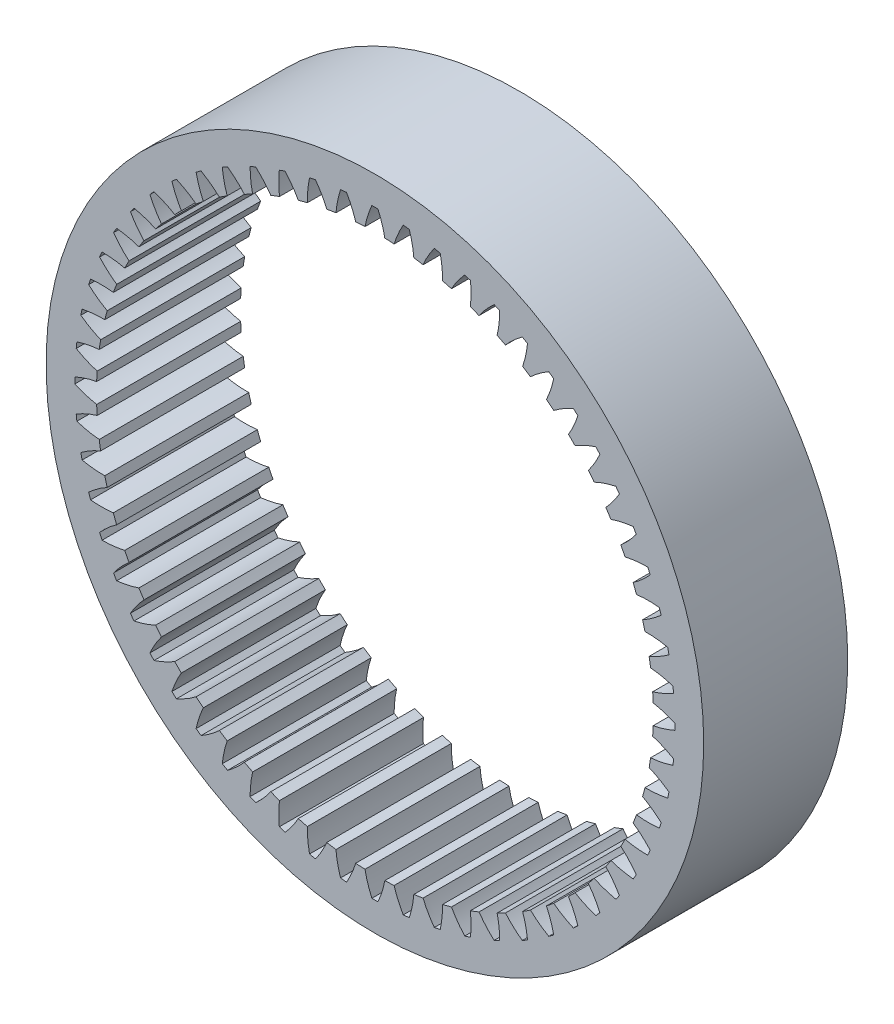
SolidWorks part; units mm, degrees
ref_plane "中间平面" through (0, 0, 0) normal (0, 0, 1) x (1, 0, 0)
ref_plane "上视基准面" through (0, 0, 0) normal (0, 1, 0) x (1, 0, 0)
ref_plane "右视基准面" through (0, 0, 0) normal (1, 0, 0) x (0, 0, -1)
sketch "直内齿圈" plane through (0, 0, 0) normal (0, 0, 1) x (1, 0, 0)
  line L2 (2.2167, 56.338) -> (0, 0)
  line L3 (0, 0) -> (0, 52) construction
  line L6 (0, 0) -> (-2.2167, 56.338)
  circle A0 centre (0, 0) radius 56.3816
  circle A1 centre (0, 0) radius 58
  arc A2 (1.5706, 59.9794) -> (-1.5706, 59.9794) centre (0, 0) ccw
  circle A3 centre (0, 0) radius 62.5
  spline S0 degree 4 poles (2.2167, 56.338) (2.2189, 56.3915) (2.2208, 56.4987) (2.2154, 56.7131) (2.1931, 57.034) (2.1521, 57.4071) (2.076, 57.9166) (1.9626, 58.5073) (1.7599, 59.3651) (1.3841, 60.63) (0.7981, 62.1958) (0.0262, 63.8633) (-0.8365, 65.4532) (-1.8681, 67.1454) (-3.5464, 69.5933) (-6.5827, 73.2746) (-11.389, 77.7718) (-17.974, 82.3547) (-25.6821, 86.2657) (-33.81, 89.1926) (-42.2136, 91.1824) (-51.2003, 92.337) (-62.4178, 92.599) (-75.7449, 91.194) (-90.8317, 87.3175) (-104.7363, 81.3291) (-115.9321, 74.8155) (-126.4728, 67.3125) (-134.6739, 60.2977) (-142.2457, 52.6107) (-149.1555, 44.336) (-154.2755, 37.3963) (-160.155, 28.3611) (-164.812, 19.8424) (-168.4497, 12.0205) (-171.2543, 5.0188) (-172.7487, 0.9762) (-174.1349, -3.1048) (-175.4127, -7.221) (-176.5824, -11.3691) (-177.6441, -15.5464) (-178.598, -19.7492) (-179.3387, -23.4474) (-179.9066, -26.6288) (-180.3354, -29.289) (-180.6516, -31.4183) (-180.9054, -33.2908) (-181.1057, -34.8874) (-181.2627, -36.2365) (-181.3797, -37.2858) (-181.5021, -38.4742) (-181.617, -39.6294) (-181.7424, -41.0512) (-181.8433, -42.2423) (-181.9548, -43.771) (-182.014, -44.6462) (-182.0826, -45.7524) (-182.1302, -46.5966) (-182.1867, -47.6884) (-182.2454, -48.9883) (-182.3019, -50.5105) (-182.3493, -52.2479) (-182.38, -53.9871) (-182.3939, -55.7257) (-182.3911, -57.4649) (-182.3716, -59.2037) (-182.3354, -60.9423) (-182.2827, -62.6805) (-182.2134, -64.4181) (-182.1277, -66.1549) (-182.0255, -67.8909) (-181.907, -69.6258) (-181.8059, -70.9261) (-181.733, -71.7926) (-181.6953, -72.2256) knots 0 0 0 0 0 0.000701 0.001401 0.002802 0.004203 0.005604 0.008133 0.010661 0.015718 0.022839 0.02996 0.034653 0.039347 0.048734 0.068727 0.096889 0.125051 0.153212 0.181374 0.209535 0.237696 0.271429 0.327752 0.384075 0.440398 0.46856 0.496721 0.553044 0.581206 0.609367 0.637529 0.66569 0.722013 0.736094 0.750174 0.764255 0.778336 0.792417 0.806497 0.820578 0.834659 0.84874 0.85578 0.86282 0.869861 0.876901 0.880421 0.883942 0.887462 0.890982 0.895509 0.900036 0.904564 0.909091 0.911932 0.914773 0.917614 0.920455 0.926136 0.931818 0.9375 0.943182 0.948864 0.954545 0.960227 0.965909 0.971591 0.977273 0.982955 0.988636 0.994318 1 1 1 1 1 construction
  spline S1 degree 4 poles (2.2167, 56.338) (2.2189, 56.3915) (2.2208, 56.4987) (2.2154, 56.7131) (2.1931, 57.034) (2.1521, 57.4071) (2.076, 57.9166) (1.9626, 58.5073) (1.7599, 59.3651) (1.3841, 60.63) (0.7981, 62.1958) (0.0262, 63.8633) (-0.8365, 65.4532) (-1.8681, 67.1454) (-3.5464, 69.5933) (-6.5827, 73.2746) (-11.389, 77.7718) (-17.974, 82.3547) (-25.6821, 86.2657) (-33.81, 89.1926) (-42.2136, 91.1824) (-51.2003, 92.337) (-62.4178, 92.599) (-75.7449, 91.194) (-90.8317, 87.3175) (-104.7363, 81.3291) (-115.9321, 74.8155) (-126.4728, 67.3125) (-134.6739, 60.2977) (-142.2457, 52.6107) (-149.1555, 44.336) (-154.2755, 37.3963) (-160.155, 28.3611) (-164.812, 19.8424) (-168.4497, 12.0205) (-171.2543, 5.0188) (-172.7487, 0.9762) (-174.1349, -3.1048) (-175.4127, -7.221) (-176.5824, -11.3691) (-177.6441, -15.5464) (-178.598, -19.7492) (-179.3387, -23.4474) (-179.9066, -26.6288) (-180.3354, -29.289) (-180.6516, -31.4183) (-180.9054, -33.2908) (-181.1057, -34.8874) (-181.2627, -36.2365) (-181.3797, -37.2858) (-181.5021, -38.4742) (-181.617, -39.6294) (-181.7424, -41.0512) (-181.8433, -42.2423) (-181.9355, -43.5066) (-181.9779, -44.1172) (-181.9987, -44.4314) knots 0 0 0 0 0 0.000701 0.001401 0.002802 0.004203 0.005604 0.008133 0.010661 0.015718 0.022839 0.02996 0.034653 0.039347 0.048734 0.068727 0.096889 0.125051 0.153212 0.181374 0.209535 0.237696 0.271429 0.327752 0.384075 0.440398 0.46856 0.496721 0.553044 0.581206 0.609367 0.637529 0.66569 0.722013 0.736094 0.750174 0.764255 0.778336 0.792417 0.806497 0.820578 0.834659 0.84874 0.85578 0.86282 0.869861 0.876901 0.880421 0.883942 0.887462 0.890982 0.895509 0.900036 0.904564 0.909091 0.909091 0.909091 0.909091 0.909091
  spline S2 degree 4 poles (-2.2167, 56.338) (-2.2189, 56.3915) (-2.2208, 56.4987) (-2.2154, 56.7131) (-2.1931, 57.034) (-2.1521, 57.4071) (-2.076, 57.9166) (-1.9626, 58.5073) (-1.7599, 59.3651) (-1.3841, 60.63) (-0.7981, 62.1958) (-0.0262, 63.8633) (0.8365, 65.4532) (1.8681, 67.1454) (3.5464, 69.5933) (6.5827, 73.2746) (11.389, 77.7718) (17.974, 82.3547) (25.6821, 86.2657) (33.81, 89.1926) (42.2136, 91.1824) (51.2003, 92.337) (62.4178, 92.599) (75.7449, 91.194) (90.8317, 87.3175) (104.7363, 81.3291) (115.9321, 74.8155) (126.4728, 67.3125) (134.6739, 60.2977) (142.2457, 52.6107) (149.1555, 44.336) (154.2755, 37.3963) (160.155, 28.3611) (164.812, 19.8424) (168.4497, 12.0205) (171.2543, 5.0188) (172.7487, 0.9762) (174.1349, -3.1048) (175.4127, -7.221) (176.5824, -11.3691) (177.6441, -15.5464) (178.598, -19.7492) (179.3387, -23.4474) (179.9066, -26.6288) (180.3354, -29.289) (180.6516, -31.4183) (180.9054, -33.2908) (181.1057, -34.8874) (181.2627, -36.2365) (181.3797, -37.2858) (181.5021, -38.4742) (181.617, -39.6294) (181.7424, -41.0512) (181.8433, -42.2423) (181.9548, -43.771) (182.014, -44.6462) (182.0826, -45.7524) (182.1302, -46.5966) (182.1867, -47.6884) (182.2454, -48.9883) (182.3019, -50.5105) (182.3493, -52.2479) (182.38, -53.9871) (182.3939, -55.7257) (182.3911, -57.4649) (182.3716, -59.2037) (182.3354, -60.9423) (182.2827, -62.6805) (182.2134, -64.4181) (182.1277, -66.1549) (182.0255, -67.8909) (181.907, -69.6258) (181.8059, -70.9261) (181.733, -71.7926) (181.6953, -72.2256) knots 0 0 0 0 0 0.000701 0.001401 0.002802 0.004203 0.005604 0.008133 0.010661 0.015718 0.022839 0.02996 0.034653 0.039347 0.048734 0.068727 0.096889 0.125051 0.153212 0.181374 0.209535 0.237696 0.271429 0.327752 0.384075 0.440398 0.46856 0.496721 0.553044 0.581206 0.609367 0.637529 0.66569 0.722013 0.736094 0.750174 0.764255 0.778336 0.792417 0.806497 0.820578 0.834659 0.84874 0.85578 0.86282 0.869861 0.876901 0.880421 0.883942 0.887462 0.890982 0.895509 0.900036 0.904564 0.909091 0.911932 0.914773 0.917614 0.920455 0.926136 0.931818 0.9375 0.943182 0.948864 0.954545 0.960227 0.965909 0.971591 0.977273 0.982955 0.988636 0.994318 1 1 1 1 1 construction
  spline S3 degree 4 poles (-2.2167, 56.338) (-2.2189, 56.3915) (-2.2208, 56.4987) (-2.2154, 56.7131) (-2.1931, 57.034) (-2.1521, 57.4071) (-2.076, 57.9166) (-1.9626, 58.5073) (-1.7599, 59.3651) (-1.3841, 60.63) (-0.7981, 62.1958) (-0.0262, 63.8633) (0.8365, 65.4532) (1.8681, 67.1454) (3.5464, 69.5933) (6.5827, 73.2746) (11.389, 77.7718) (17.974, 82.3547) (25.6821, 86.2657) (33.81, 89.1926) (42.2136, 91.1824) (51.2003, 92.337) (62.4178, 92.599) (75.7449, 91.194) (90.8317, 87.3175) (104.7363, 81.3291) (115.9321, 74.8155) (126.4728, 67.3125) (134.6739, 60.2977) (142.2457, 52.6107) (149.1555, 44.336) (154.2755, 37.3963) (160.155, 28.3611) (164.812, 19.8424) (168.4497, 12.0205) (171.2543, 5.0188) (172.7487, 0.9762) (174.1349, -3.1048) (175.4127, -7.221) (176.5824, -11.3691) (177.6441, -15.5464) (178.598, -19.7492) (179.3387, -23.4474) (179.9066, -26.6288) (180.3354, -29.289) (180.6516, -31.4183) (180.9054, -33.2908) (181.1057, -34.8874) (181.2627, -36.2365) (181.3797, -37.2858) (181.5021, -38.4742) (181.617, -39.6294) (181.7424, -41.0512) (181.8433, -42.2423) (181.9355, -43.5066) (181.9779, -44.1172) (181.9987, -44.4314) knots 0 0 0 0 0 0.000701 0.001401 0.002802 0.004203 0.005604 0.008133 0.010661 0.015718 0.022839 0.02996 0.034653 0.039347 0.048734 0.068727 0.096889 0.125051 0.153212 0.181374 0.209535 0.237696 0.271429 0.327752 0.384075 0.440398 0.46856 0.496721 0.553044 0.581206 0.609367 0.637529 0.66569 0.722013 0.736094 0.750174 0.764255 0.778336 0.792417 0.806497 0.820578 0.834659 0.84874 0.85578 0.86282 0.869861 0.876901 0.880421 0.883942 0.887462 0.890982 0.895509 0.900036 0.904564 0.909091 0.909091 0.909091 0.909091 0.909091
  point P8 (0, 60)
  dimension "基圆直径" = 112.7631
  dimension "齿顶圆" = 116
  dimension "分度圆" = 120
  dimension "齿根圆" = 125
  dimension "D1" = 3.1416
sketch "圆" plane through (0, 0, 0) normal (0, 0, 1) x (1, 0, 0)
  circle A1 centre (0, 0) radius 68.5
  circle A2 centre (0, 0) radius 58 construction
  circle A3 centre (0, 0) radius 58
  dimension "D1" = 137
extrude "毛胚" add sketch "圆" along normal mid plane 30
chamfer "轮齿倒角" [suppressed] distance 0.001 angle 45
sketch "齿形" plane through (0, 0, 0) normal (0, 0, 1) x (1, 0, 0)
  line L4 (0, 0) -> (-2.2167, 56.338) construction
  line L5 (2.2167, 56.338) -> (0, 0) construction
  line L6 (0, 0) -> (-2.2167, 56.338)
  line L7 (2.2167, 56.338) -> (0, 0)
  circle A4 centre (0, 0) radius 58 construction
  circle A5 centre (0, 0) radius 62.5 construction
  circle A6 centre (0, 0) radius 58
  circle A7 centre (0, 0) radius 62.5
  spline S1 degree 4 poles (-1995.8108, -87.8377) (43.9441, 50.7725) (-0.8416, 50.9897) (-2.4035, 54.0015) (-2.1931, 57.034) (-2.1521, 57.4071) (-2.076, 57.9166) (-1.9626, 58.5073) (-1.7599, 59.3651) (-1.3841, 60.63) (-0.7981, 62.1958) (-0.0262, 63.8633) (0.8365, 65.4532) (1.8681, 67.1454) (3.5464, 69.5933) (6.5827, 73.2746) (11.389, 77.7718) (17.974, 82.3547) (25.6821, 86.2657) (33.81, 89.1926) (42.2136, 91.1824) (51.2003, 92.337) (62.4178, 92.599) (75.7449, 91.194) (90.8317, 87.3175) (104.7363, 81.3291) (115.9321, 74.8155) (126.4728, 67.3125) (134.6739, 60.2977) (142.2457, 52.6107) (149.1555, 44.336) (154.2755, 37.3963) (160.155, 28.3611) (164.812, 19.8424) (168.4497, 12.0205) (171.2543, 5.0188) (172.7487, 0.9762) (174.1349, -3.1048) (175.4127, -7.221) (176.5824, -11.3691) (177.6441, -15.5464) (178.598, -19.7492) (179.3387, -23.4474) (179.9066, -26.6288) (180.3354, -29.289) (180.6516, -31.4183) (180.9054, -33.2908) (181.1057, -34.8874) (181.2627, -36.2365) (181.3797, -37.2858) (181.5021, -38.4742) (181.617, -39.6294) (181.7424, -41.0512) (182.1176, -45.4798) (182.8201, -57.5451) (176.7388, 30.3447) (313.9302, -2039.1996) knots -0.035513 -0.035513 -0.035513 -0.035513 -0.035513 0.000701 0.001401 0.002802 0.004203 0.005604 0.008133 0.010661 0.015718 0.022839 0.02996 0.034653 0.039347 0.048734 0.068727 0.096889 0.125051 0.153212 0.181374 0.209535 0.237696 0.271429 0.327752 0.384075 0.440398 0.46856 0.496721 0.553044 0.581206 0.609367 0.637529 0.66569 0.722013 0.736094 0.750174 0.764255 0.778336 0.792417 0.806497 0.820578 0.834659 0.84874 0.85578 0.86282 0.869861 0.876901 0.880421 0.883942 0.887462 0.890982 0.895509 0.900036 0.904564 0.958315 0.958315 0.958315 0.958315 0.958315 only from (-2.2167, 56.338) to (181.9987, -44.4314) construction
  spline S3 degree 4 poles (1995.8108, -87.8377) (-43.9441, 50.7725) (0.8416, 50.9897) (2.4035, 54.0015) (2.1931, 57.034) (2.1521, 57.4071) (2.076, 57.9166) (1.9626, 58.5073) (1.7599, 59.3651) (1.3841, 60.63) (0.7981, 62.1958) (0.0262, 63.8633) (-0.8365, 65.4532) (-1.8681, 67.1454) (-3.5464, 69.5933) (-6.5827, 73.2746) (-11.389, 77.7718) (-17.974, 82.3547) (-25.6821, 86.2657) (-33.81, 89.1926) (-42.2136, 91.1824) (-51.2003, 92.337) (-62.4178, 92.599) (-75.7449, 91.194) (-90.8317, 87.3175) (-104.7363, 81.3291) (-115.9321, 74.8155) (-126.4728, 67.3125) (-134.6739, 60.2977) (-142.2457, 52.6107) (-149.1555, 44.336) (-154.2755, 37.3963) (-160.155, 28.3611) (-164.812, 19.8424) (-168.4497, 12.0205) (-171.2543, 5.0188) (-172.7487, 0.9762) (-174.1349, -3.1048) (-175.4127, -7.221) (-176.5824, -11.3691) (-177.6441, -15.5464) (-178.598, -19.7492) (-179.3387, -23.4474) (-179.9066, -26.6288) (-180.3354, -29.289) (-180.6516, -31.4183) (-180.9054, -33.2908) (-181.1057, -34.8874) (-181.2627, -36.2365) (-181.3797, -37.2858) (-181.5021, -38.4742) (-181.617, -39.6294) (-181.7424, -41.0512) (-182.1176, -45.4798) (-182.8201, -57.5451) (-176.7388, 30.3447) (-313.9302, -2039.1996) knots -0.035513 -0.035513 -0.035513 -0.035513 -0.035513 0.000701 0.001401 0.002802 0.004203 0.005604 0.008133 0.010661 0.015718 0.022839 0.02996 0.034653 0.039347 0.048734 0.068727 0.096889 0.125051 0.153212 0.181374 0.209535 0.237696 0.271429 0.327752 0.384075 0.440398 0.46856 0.496721 0.553044 0.581206 0.609367 0.637529 0.66569 0.722013 0.736094 0.750174 0.764255 0.778336 0.792417 0.806497 0.820578 0.834659 0.84874 0.85578 0.86282 0.869861 0.876901 0.880421 0.883942 0.887462 0.890982 0.895509 0.900036 0.904564 0.958315 0.958315 0.958315 0.958315 0.958315 only from (2.2167, 56.338) to (-181.9987, -44.4314) construction
  spline S4 degree 4 poles (-2.2167, 56.338) (-2.2189, 56.3915) (-2.2208, 56.4987) (-2.2154, 56.7131) (-2.1931, 57.034) (-2.1521, 57.4071) (-2.076, 57.9166) (-1.9626, 58.5073) (-1.7599, 59.3651) (-1.3841, 60.63) (-0.7981, 62.1958) (-0.0262, 63.8633) (0.8365, 65.4532) (1.8681, 67.1454) (3.5464, 69.5933) (6.5827, 73.2746) (11.389, 77.7718) (17.974, 82.3547) (25.6821, 86.2657) (33.81, 89.1926) (42.2136, 91.1824) (51.2003, 92.337) (62.4178, 92.599) (75.7449, 91.194) (90.8317, 87.3175) (104.7363, 81.3291) (115.9321, 74.8155) (126.4728, 67.3125) (134.6739, 60.2977) (142.2457, 52.6107) (149.1555, 44.336) (154.2755, 37.3963) (160.155, 28.3611) (164.812, 19.8424) (168.4497, 12.0205) (171.2543, 5.0188) (172.7487, 0.9762) (174.1349, -3.1048) (175.4127, -7.221) (176.5824, -11.3691) (177.6441, -15.5464) (178.598, -19.7492) (179.3387, -23.4474) (179.9066, -26.6288) (180.3354, -29.289) (180.6516, -31.4183) (180.9054, -33.2908) (181.1057, -34.8874) (181.2627, -36.2365) (181.3797, -37.2858) (181.5021, -38.4742) (181.617, -39.6294) (181.7424, -41.0512) (181.8433, -42.2423) (181.9355, -43.5066) (181.9779, -44.1172) (181.9987, -44.4314) knots 0 0 0 0 0 0.000701 0.001401 0.002802 0.004203 0.005604 0.008133 0.010661 0.015718 0.022839 0.02996 0.034653 0.039347 0.048734 0.068727 0.096889 0.125051 0.153212 0.181374 0.209535 0.237696 0.271429 0.327752 0.384075 0.440398 0.46856 0.496721 0.553044 0.581206 0.609367 0.637529 0.66569 0.722013 0.736094 0.750174 0.764255 0.778336 0.792417 0.806497 0.820578 0.834659 0.84874 0.85578 0.86282 0.869861 0.876901 0.880421 0.883942 0.887462 0.890982 0.895509 0.900036 0.904564 0.909091 0.909091 0.909091 0.909091 0.909091
  spline S5 degree 4 poles (2.2167, 56.338) (2.2189, 56.3915) (2.2208, 56.4987) (2.2154, 56.7131) (2.1931, 57.034) (2.1521, 57.4071) (2.076, 57.9166) (1.9626, 58.5073) (1.7599, 59.3651) (1.3841, 60.63) (0.7981, 62.1958) (0.0262, 63.8633) (-0.8365, 65.4532) (-1.8681, 67.1454) (-3.5464, 69.5933) (-6.5827, 73.2746) (-11.389, 77.7718) (-17.974, 82.3547) (-25.6821, 86.2657) (-33.81, 89.1926) (-42.2136, 91.1824) (-51.2003, 92.337) (-62.4178, 92.599) (-75.7449, 91.194) (-90.8317, 87.3175) (-104.7363, 81.3291) (-115.9321, 74.8155) (-126.4728, 67.3125) (-134.6739, 60.2977) (-142.2457, 52.6107) (-149.1555, 44.336) (-154.2755, 37.3963) (-160.155, 28.3611) (-164.812, 19.8424) (-168.4497, 12.0205) (-171.2543, 5.0188) (-172.7487, 0.9762) (-174.1349, -3.1048) (-175.4127, -7.221) (-176.5824, -11.3691) (-177.6441, -15.5464) (-178.598, -19.7492) (-179.3387, -23.4474) (-179.9066, -26.6288) (-180.3354, -29.289) (-180.6516, -31.4183) (-180.9054, -33.2908) (-181.1057, -34.8874) (-181.2627, -36.2365) (-181.3797, -37.2858) (-181.5021, -38.4742) (-181.617, -39.6294) (-181.7424, -41.0512) (-181.8433, -42.2423) (-181.9355, -43.5066) (-181.9779, -44.1172) (-181.9987, -44.4314) knots 0 0 0 0 0 0.000701 0.001401 0.002802 0.004203 0.005604 0.008133 0.010661 0.015718 0.022839 0.02996 0.034653 0.039347 0.048734 0.068727 0.096889 0.125051 0.153212 0.181374 0.209535 0.237696 0.271429 0.327752 0.384075 0.440398 0.46856 0.496721 0.553044 0.581206 0.609367 0.637529 0.66569 0.722013 0.736094 0.750174 0.764255 0.778336 0.792417 0.806497 0.820578 0.834659 0.84874 0.85578 0.86282 0.869861 0.876901 0.880421 0.883942 0.887462 0.890982 0.895509 0.900036 0.904564 0.909091 0.909091 0.909091 0.909091 0.909091
extrude "插齿" cut sketch "齿形" against normal mid plane 30 contours A6 S5 A7 S4 region at (0, 59.8696, 0)
pattern_circular "圆周阵列" count 60 over 360 about axis through (0, 0, 15) along (0, 0, -1) of "插齿"
sketch "分度圆" plane through (0, 0, 0) normal (0, 0, 1) x (1, 0, 0)
  circle A0 centre (0, 0) radius 60 construction
  circle A1 centre (0, 0) radius 60 construction
equation "\"D1\"= \"R\""
equation "\"m\"= 2'模数"
equation "\"z\"= 60'齿数"
equation "\"a\"= 20'压力角（常见为20°，一般不用修改）"
equation "\"B\"= 30'齿宽"
equation "\"D\"= 115'大圆值径（必须大于齿根圆，否则自动修正）"
equation "\"d1\"= 0'内径（若设为0或负数，则自动计算）"
equation "\"C1\"= 0'轮齿倒角（若设为0，则无倒角）"
equation "\"x\"= 0'变位系数（不懂勿动）"
equation "\"ha\"= 1'齿顶高系数（不懂勿动）"
equation "\"c\"= 0.25'顶隙系数（不懂勿动）"
equation "\"基圆直径@直内齿圈\" = \"m\" * \"z\" * cos ( \"a\" ) "
equation "\"齿顶圆@直内齿圈\" = IIF ( \"d1\" > 0 , \"d1\" , \"m\" *  ( \"z\" - 2 *  ( \"ha\" + \"x\" )  )  ) "
equation "\"分度圆@直内齿圈\" = \"m\" * \"z\""
equation "\"齿根圆@直内齿圈\" = \"m\" *  ( \"z\" + 2 *  ( \"ha\" + \"x\" + \"c\" )  ) "
equation "\"D1@毛胚\" = \"B\""
equation "\"D1@轮齿倒角\"= IIF ( \"C1\" > 0 , \"C1\" , 0.001 )"
equation "\"轮齿倒角\"= IIF ( \"C1\" > 0 , \"unsuppressed\" , \"suppressed\" )"
equation "\"D1@插齿\" = \"B\""
equation "\"D1@直内齿圈\" = \"m\" *  ( pi / 2 )  - 2 * \"m\" * tan ( \"a\" )  * \"x\""
equation "\"D1@圆周阵列\" = \"z\""
equation "\"D1@圆\"= IIF ( \"D\" > \"m\" * ( \"z\" + 2 * ( \"ha\" + \"x\" + \"c\" ) ) , \"D\" , int ( 1.1 * \"m\" * ( \"z\" + 2 * ( \"ha\" + \"x\" + \"c\" ) ) ) )"
